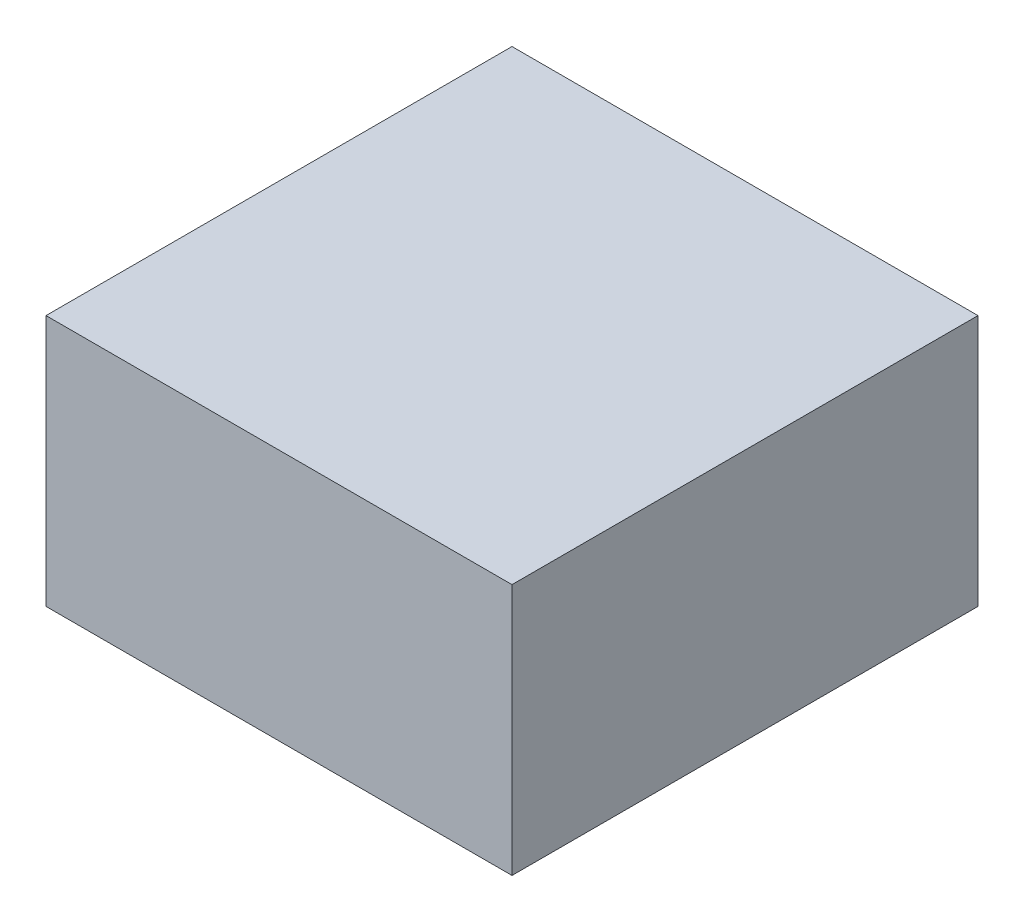
SolidWorks part; units mm, degrees
note: The reader was unsure of these and kept them because the rebuilt part matched: shared geometry of "草图1<5>", "草图1<8>".
ref_plane "前视基准面" through (0, 0, 0) normal (0, 0, 1) x (1, 0, 0)
ref_plane "上视基准面" through (0, 0, 0) normal (0, 1, 0) x (1, 0, 0)
ref_plane "右视基准面" through (0, 0, 0) normal (1, 0, 0) x (0, 0, -1)
other "Configuration Table"
sketch "草图1" plane through (-54.4523, 0, -10.1113) normal (0, 1, 0) x (1, 0, 0)
  line L0 (-9.483, 9.4487) -> (9.017, -9.0513) construction
  line L9 (-9.483, 9.4487) -> (9.017, 9.4487)
  line L10 (-9.483, 9.4487) -> (-9.483, -9.0513)
  line L11 (-9.483, -9.0513) -> (9.017, -9.0513)
  line L12 (9.017, 9.4487) -> (9.017, -9.0513)
  line L13 (-7.733, 7.6987) -> (7.267, 7.6987)
  line L14 (-7.733, 7.6987) -> (-7.733, -7.3013)
  line L15 (-7.733, -7.3013) -> (7.267, -7.3013)
  line L16 (7.267, 7.6987) -> (7.267, -7.3013)
  line L17 (9.017, 9.4487) -> (-9.483, -9.0513) construction
  line L18 (-7.733, 7.6987) -> (7.267, -7.3013) construction
  line L19 (7.267, 7.6987) -> (-7.733, -7.3013) construction
  line L20 (-34.6316, 13.1242) -> (-30.6316, 12.1242) construction
  line L21 (-34.6316, 13.1242) -> (-30.6316, 13.1242)
  line L22 (-34.6316, 13.1242) -> (-34.6316, 12.1242)
  line L23 (-34.6316, 12.1242) -> (-30.6316, 12.1242)
  line L24 (-30.6316, 13.1242) -> (-30.6316, 12.1242)
  line L25 (-34.6316, 12.1242) -> (-30.6316, 13.1242) construction
  line L26 (-33.1316, 10.5843) -> (-33.1316, 14.5843)
  line L27 (-33.1316, 10.5843) -> (-32.1316, 10.5843)
  line L28 (-32.1316, 10.5843) -> (-32.1316, 14.5843)
  line L29 (-33.1316, 14.5843) -> (-32.1316, 14.5843)
  line L30 (-33.1316, 10.5843) -> (-32.1316, 14.5843) construction
  line L31 (-32.1316, 10.5843) -> (-33.1316, 14.5843) construction
  circle A0 centre (-32.6316, 12.5843) radius 3
  dimension "D5" = 6
  dimension "D1" = 18.5
  dimension "D2" = 18.5
  dimension "D3" = 15
  dimension "D4" = 15
  dimension "D6" = 4
  dimension "D7" = 1
extrude "凸台-拉伸2" add sketch "草图1" along normal blind 10 contours L9 L12 L11 L10
extrude "切除-拉伸1" cut sketch "草图1<5>" along normal blind 8 and the other way blind 10 contours L16 L13 L14 L15
sketch "草图1<5>" plane through (-54.4523, 0, -10.1113) normal (0, 1, 0) x (1, 0, 0) same geometry as "草图1"
extrude "凸台-拉伸3" add sketch "草图1<8>" along normal blind 8 separate body contours A0 | L23 L24 L21 L22 | L28 L29 L26 L27
sketch "草图1<8>" plane through (-54.4523, 0, -10.1113) normal (0, 1, 0) x (1, 0, 0) same geometry as "草图1"
delete or keep bodies "实体-删除/保留 1" type delete bodies bodies 109
sketch "草图2" plane through (0, 0, 0) normal (0, 1, 0) x (1, 0, 0)
  line L1 (-135.2154, -15.1378) -> (-118.7154, -15.1378)
  line L2 (-136.2154, -16.1378) -> (-136.2154, -32.6378)
  line L3 (-135.2154, -33.6378) -> (-118.7154, -33.6378)
  line L4 (-117.7154, -16.1378) -> (-117.7154, -32.6378)
  arc A0 (-118.7154, -15.1378) -> (-117.7154, -16.1378) centre (-118.7154, -16.1378) cw
  arc A1 (-118.7154, -33.6378) -> (-117.7154, -32.6378) centre (-118.7154, -32.6378) ccw
  arc A2 (-136.2154, -32.6378) -> (-135.2154, -33.6378) centre (-135.2154, -32.6378) ccw
  arc A3 (-135.2154, -15.1378) -> (-136.2154, -16.1378) centre (-135.2154, -16.1378) ccw
  point P6 (-117.7154, -15.1378)
  point P9 (-117.7154, -33.6378)
  point P14 (-136.2154, -15.1378)
  dimension "D3" = 1
  dimension "D4" = 1
  dimension "D5" = 1
  dimension "D6" = 1
  dimension "D1" = 18.5
  dimension "D2" = 18.5
